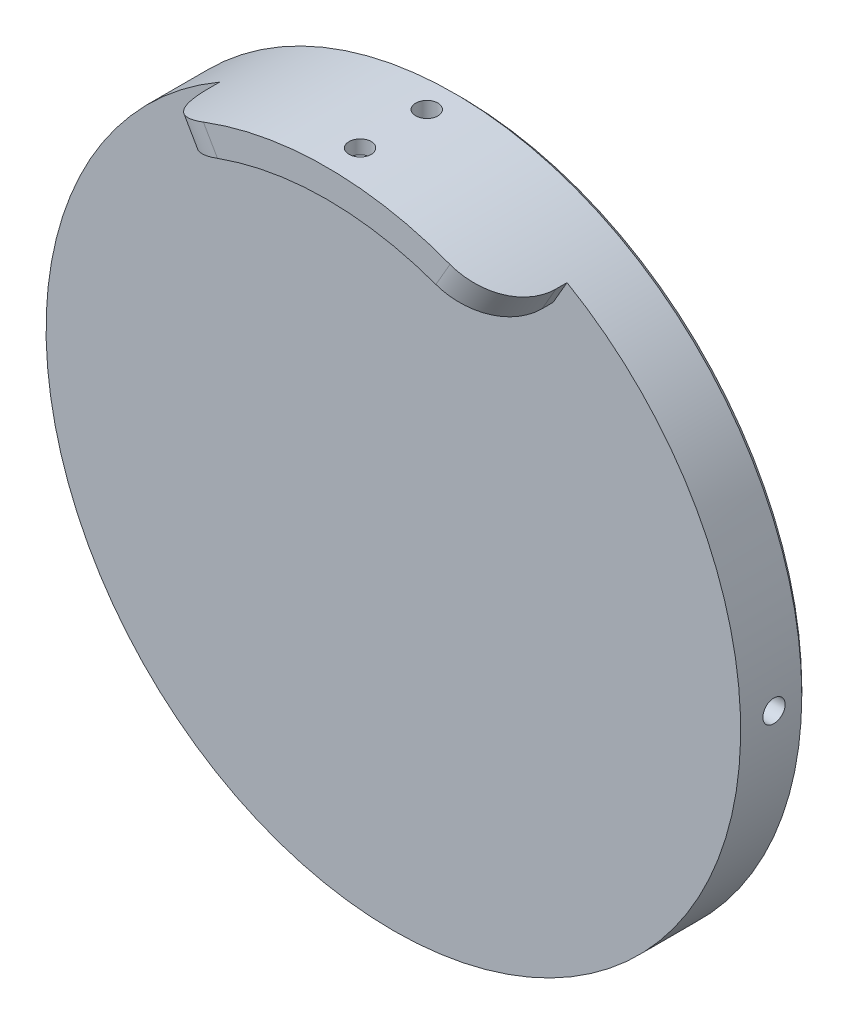
SolidWorks part; units mm, degrees
material "6063-T6"
ref_plane "Ön Düzlem" through (0, 0, 0) normal (0, 0, 1) x (1, 0, 0)
ref_plane "Üst Düzlem" through (0, 0, 0) normal (0, 1, 0) x (1, 0, 0)
ref_plane "Sağ Düzlem" through (0, 0, 0) normal (1, 0, 0) x (0, 0, -1)
sketch "Sketch1" plane through (0, 0, 0) normal (0, 0, 1) x (1, 0, 0)
  circle A0 centre (0, 0) radius 62.5
extrude "Boss-Extrude1" add sketch "Sketch1" along normal mid plane 12
sketch "Sketch2" plane through (0, 0, 0) normal (0, 1, 0) x (1, 0, 0)
  circle A0 centre (0, 0) radius 2
extrude "Cut-Extrude1" cut sketch "Sketch2" along normal blind 13 from offset 55
extrude "Cut-Extrude2" cut sketch "Sketch2<2>" against normal blind 13 from offset 55 offset against normal yes
sketch "Sketch2<2>" plane through (0, 0, 0) normal (0, 1, 0) x (1, 0, 0) same geometry as "Sketch2"
sketch "Sketch3" plane through (0, 0, 0) normal (1, 0, 0) x (0, 0, -1)
  circle A0 centre (0, 0) radius 2
  dimension "D1" = 4
extrude "Cut-Extrude3" cut sketch "Sketch3" along normal blind 13 from offset 55
extrude "Cut-Extrude4" cut sketch "Sketch3<2>" against normal blind 13 from offset 55 offset against normal yes
sketch "Sketch3<2>" plane through (0, 0, 0) normal (1, 0, 0) x (0, 0, -1) same geometry as "Sketch3"
sketch "Sketch5" plane through (0, 0, 6) normal (0, 0, 1) x (1, 0, 0)
  line L0 (-31.25, 54.1266) -> (0, 0) construction
  line L1 (0, 0) -> (31.25, 54.1266) construction
  line L2 (0, 0) -> (0, 62.5) construction
  line L3 (-31.25, 54.1266) -> (-28.75, 49.7965)
  line L4 (31.25, 54.1266) -> (28.75, 49.7965)
  arc A0 (28.75, 49.7965) -> (-28.75, 49.7965) centre (0, 0) ccw
  arc A1 (31.25, 54.1266) -> (-31.25, 54.1266) centre (0, 0) ccw
  dimension "D1" = 5
  dimension "D2" = 125
  dimension "D3" = 30
  dimension "D4" = 60
extrude "Boss-Extrude2" add sketch "Sketch5" along normal blind 12
fillet "Fillet1" radius 10 2 edges at (-30, 51.9615, 18) (30, 51.9615, 18)
sketch "Sketch6" plane through (0, 0, 0) normal (0, 1, 0) x (1, 0, 0)
  line L0 (-31.25, -6) -> (31.25, -6) construction
  line L1 (0, -6) -> (0, -12) construction
  circle A0 centre (0, -12) radius 2
  dimension "D2" = 4
  dimension "D1" = 6
extrude "Cut-Extrude8" cut sketch "Sketch6" along normal blind 12.5 from offset 60
chamfer "Chamfer1" distance 1 angle 45 1 edges at (62.5, 0, -6)
